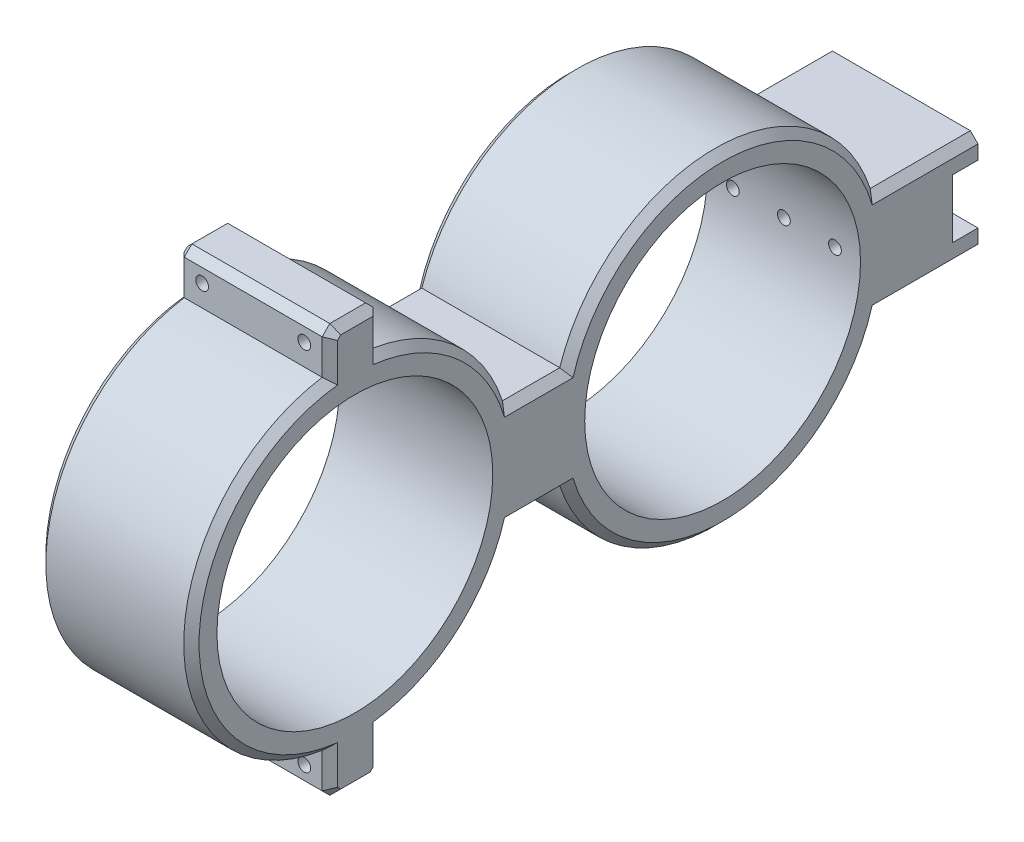
SolidWorks part; units mm, degrees
ref_plane "前视基准面" through (0, 0, 0) normal (0, 0, 1) x (1, 0, 0)
ref_plane "上视基准面" through (0, 0, 0) normal (0, 1, 0) x (1, 0, 0)
ref_plane "右视基准面" through (0, 0, 0) normal (1, 0, 0) x (0, 0, -1)
sketch "草图2" plane through (0, 0, 0) normal (1, 0, 0) x (0, 0, -1)
  circle A0 centre (0, 0) radius 32
  dimension "D1" = 64
extrude "凸台-拉伸1" add sketch "草图2" along normal blind 30
sketch "草图3" plane through (30, 0, 0) normal (1, 0, 0) x (0, 0, -1)
  circle A0 centre (0, 0) radius 27
  dimension "D1" = 54
extrude "切除-拉伸1" cut sketch "草图3" against normal through all
sketch "草图4" plane through (30, 0, 0) normal (1, 0, 0) x (0, 0, -1)
  line L1 (25.0799, 10) -> (117, 10)
  line L2 (25.0799, 10) -> (25.0799, -10)
  line L3 (25.0799, -10) -> (117, -10)
  line L4 (117, 10) -> (117, -10)
  line L5 (25.0799, 10) -> (117, -10) construction
  line L6 (25.0799, -10) -> (117, 10) construction
  circle A0 centre (0, 0) radius 27 construction
  circle A1 centre (0, 0) radius 32 construction
  point P0 (71.0399, 0)
  dimension "D1" = 117
  dimension "D2" = 20
extrude "凸台-拉伸2" add sketch "草图4" against normal blind 30
sketch "草图5" plane through (30, 0, 0) normal (1, 0, 0) x (0, 0, -1)
  circle A0 centre (0, 0) radius 27
  dimension "D1" = 54
extrude "切除-拉伸2" cut sketch "草图5" against normal through all
sketch "草图6" plane through (0, 0, -117) normal (0, 0, -1) x (-1, 0, 0)
  line L0 (0, 10) -> (-30, 10) construction
  line L1 (0, 5.75) -> (-30, 5.75)
  line L2 (0, 5.75) -> (0, 10)
  line L3 (0, 10) -> (-30, 10)
  line L4 (-30, 5.75) -> (-30, 10)
  line L5 (0, 5.75) -> (-30, 10) construction
  line L6 (0, 10) -> (-30, 5.75) construction
  line L7 (-30, -10) -> (-30, 10) construction
  line L8 (0, -10) -> (0, 10) construction
  line L9 (-30, 0) -> (0, 0) construction
  line L10 (0, -10) -> (-30, -10)
  line L11 (-30, -5.75) -> (-30, -10)
  line L12 (0, -5.75) -> (-30, -5.75)
  line L13 (0, -5.75) -> (0, -10)
  point P0 (-15, 7.875)
  dimension "D1" = 11.5
extrude "凸台-拉伸3" add sketch "草图6" along normal blind 5
sketch "草图8" plane through (30, 0, 0) normal (1, 0, 0) x (0, 0, -1)
  line L0 (-32, 0) -> (117, 0) construction
  line L1 (5.0998, 26.5516) -> (-4.9002, 26.5516)
  line L2 (5.0998, 26.5516) -> (5.0998, 40)
  line L3 (5.0998, 40) -> (-4.9002, 40)
  line L4 (-4.9002, 26.5516) -> (-4.9002, 40)
  line L5 (5.0998, 26.5516) -> (-4.9002, 40) construction
  line L6 (5.0998, 40) -> (-4.9002, 26.5516) construction
  line L7 (117, -5.75) -> (117, 5.75) construction
  line L8 (5.0998, -40) -> (-4.9002, -40)
  line L9 (-4.9002, -26.5516) -> (-4.9002, -40)
  line L10 (5.0998, -26.5516) -> (-4.9002, -26.5516)
  line L11 (5.0998, -26.5516) -> (5.0998, -40)
  line L12 (0.0998, 50.6797) -> (0.0998, -34.5244) construction
  circle A0 centre (0, 0) radius 27 construction
  arc A1 (30.3974, 10) -> (30.3974, -10) centre (0, 0) ccw construction
  arc A2 (30.3974, 10) -> (30.3974, -10) centre (0, 0) ccw construction
  point P0 (0.0998, 33.2758)
  dimension "D1" = 10
  dimension "D2" = 40
extrude "凸台-拉伸4" add sketch "草图8" against normal blind 30
sketch "草图9" plane through (0, 0, 4.9002) normal (0, 0, 1) x (1, 0, 0)
  line L0 (0, 35.8113) -> (30, 35.8113) construction
  line L1 (0, 40) -> (0, 31.6226) construction
  line L2 (30, 40) -> (30, 31.6226) construction
  line L3 (15, 40) -> (15, 31.6226) construction
  line L4 (0, 40) -> (30, 40) construction
  line L5 (30, 31.6226) -> (0, 31.6226) construction
  line L6 (0, 0) -> (28.5789, 0) construction
  circle A0 centre (5, 35.8113) radius 1.25
  circle A1 centre (25, 35.8113) radius 1.25
  circle A2 centre (25, -35.8113) radius 1.25
  circle A3 centre (5, -35.8113) radius 1.25
  dimension "D1" = 2.5
  dimension "D2" = 2.5
  dimension "D3" = 5
extrude "切除-拉伸4" cut sketch "草图9" against normal up to next
sketch "草图10" plane through (30, 0, 0) normal (1, 0, 0) x (0, 0, -1)
  circle A0 centre (0, 0) radius 27
  dimension "D1" = 54
extrude "切除-拉伸5" cut sketch "草图10" against normal through all
chamfer "倒角2" distance 1.5 angle 45 4 edges at (15, -40, 4.9002) (15, -40, -5.0998) (15, 40, -5.0998) (15, 40, 4.9002)
chamfer "倒角3" distance 1.5 angle 45 25 edges at (0, -24.3402, -20.7739) (30, -35.0455, -5.0998) (0, -35.0455, -5.0998) (0, -39.25, -4.3498) (30, -40, -0.0998) (0, -40, -0.0998) (0, -39.25, 4.1502) (0, -35.0613, 4.9002) (30, -35.0613, 4.9002) (0, 24.3402, -20.7739) (0, 35.0455, -5.0998) (30, 35.0455, -5.0998) (0, 39.25, -4.3498) (30, 40, -0.0998) (0, 40, -0.0998) (0, 39.25, 4.1502) (30, 35.0613, 4.9002) (0, 35.0613, 4.9002) (0, 0, 32) (30, 24.3402, -20.7739) (30, -24.3402, -20.7739) (30, -39.25, -4.3498) (30, -39.25, 4.1502) (30, 39.25, 4.1502) (30, 0, 32)
sketch "草图13" plane through (30, 0, 0) normal (1, 0, 0) x (0, 0, -1)
  line L0 (117, 0) -> (27, 0) construction
  line L1 (117, -5.75) -> (117, 5.75) construction
  circle A0 centre (72, 0) radius 32
  circle A1 centre (0, 0) radius 27 construction
  point P9 (0, 0)
  dimension "D1" = 64
extrude "凸台-拉伸5" add sketch "草图13" against normal blind 30
sketch "草图14" plane through (30, 0, 0) normal (1, 0, 0) x (0, 0, -1)
  circle A0 centre (72, 0) radius 27
  arc A1 (102.3974, 10) -> (41.6026, 10) centre (72, 0) ccw construction
  dimension "D1" = 54
extrude "切除-拉伸8" cut sketch "草图14" against normal through all
chamfer "倒角4" distance 1.5 angle 45 16 edges at (0, -10, -35.2083) (0, 10, -112.1987) (30, -10, -35.2083) (30, 10, -112.1987) (30, 10, -35.2083) (0, 10, -35.2083) (0, -10, -112.1987) (30, -10, -112.1987) (0, -32, -72) (30, -32, -72) (0, 32, -72) (30, 32, -72)
sketch "草图7" plane through (0, 0, -117) normal (0, 0, -1) x (-1, 0, 0)
  line L0 (-15, -5.75) -> (-15, 5.75) construction
  line L3 (0, -5.75) -> (-30, -5.75) construction
  line L4 (-30, 5.75) -> (0, 5.75) construction
  line L5 (-30, 0) -> (0, 0) construction
  line L6 (-30, -5.75) -> (-30, 5.75) construction
  line L7 (0, -5.75) -> (0, 5.75) construction
  circle A0 centre (-15, 0) radius 1.25
  circle A1 centre (-5, 0) radius 1.25
  circle A2 centre (-25, 0) radius 1.25
  dimension "D1" = 2.5
  dimension "D2" = 5
extrude "切除-拉伸3" cut sketch "草图7" against normal blind 30
sketch "草图11" plane through (0, 0, 0) normal (0, 0, 1) x (1, 0, 0)
  line L1 (60.6516, -49.0819) -> (-27.9407, -49.0819)
  line L2 (60.6516, -49.0819) -> (60.6516, 47.2432)
  line L3 (60.6516, 47.2432) -> (-27.9407, 47.2432)
  line L4 (-27.9407, -49.0819) -> (-27.9407, 47.2432)
  line L5 (60.6516, -49.0819) -> (-27.9407, 47.2432) construction
  line L6 (60.6516, 47.2432) -> (-27.9407, -49.0819) construction
  point P0 (16.3554, -0.9194)
extrude "切除-拉伸9" [suppressed] cut sketch "草图11" against normal through all
sketch "草图16" [suppressed] plane through (0, 0, 0) normal (0, 0, -1) x (-1, 0, 0)
  circle A0 centre (-25, 35.8113) radius 1.5
  circle A1 centre (-5, 35.8113) radius 1.5
  circle A2 centre (-5, -35.8113) radius 1.5
  circle A3 centre (-25, -35.8113) radius 1.5
  dimension "D1" = 3
extrude "切除-拉伸10" [suppressed] cut sketch "草图16" against normal up to next
